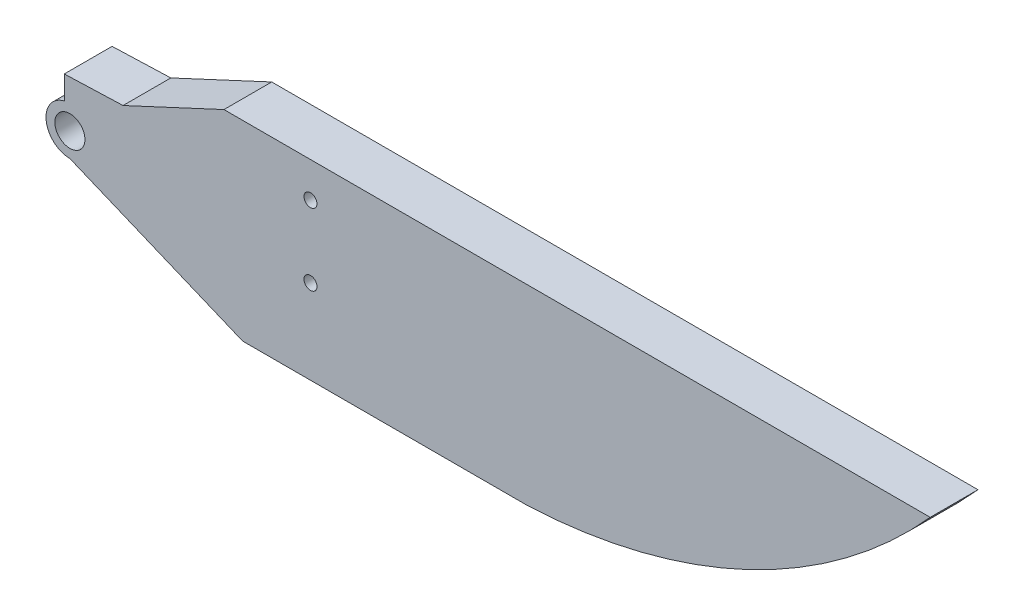
SolidWorks part; units mm, degrees
ref_plane "Front Plane" through (0, 0, 0) normal (0, 0, 1) x (1, 0, 0)
ref_plane "Top Plane" through (0, 0, 0) normal (0, 1, 0) x (1, 0, 0)
ref_plane "Right Plane" through (0, 0, 0) normal (1, 0, 0) x (0, 0, -1)
sketch "Sketch1" plane through (0, 0, 0) normal (0, 0, 1) x (1, 0, 0)
  line L1 (120.65, 25.4) -> (-120.65, 25.4)
  line L2 (120.65, 25.4) -> (120.65, -25.4)
  line L3 (120.65, -25.4) -> (-120.65, -25.4)
  line L4 (-120.65, 25.4) -> (-120.65, -25.4)
  line L5 (120.65, 25.4) -> (-120.65, -25.4) construction
  line L6 (120.65, -25.4) -> (-120.65, 25.4) construction
  point P0 (0, 0)
  dimension "D1" = 241.3
  dimension "D2" = 50.8
extrude "Boss-Extrude1" add sketch "Sketch1" along normal blind 12.7
sketch "Sketch3" plane through (0, 0, 12.7) normal (0, 0, 1) x (1, 0, 0)
  line L0 (0, 0) -> (-120.65, 0) construction
  line L1 (-120.65, 25.4) -> (-120.65, -25.4) construction
  circle A0 centre (-107.95, 0) radius 4
  dimension "D2" = 8
  dimension "D1" = 12.7
extrude "Cut-Extrude1" cut sketch "Sketch3" against normal through all
sketch "Sketch5" plane through (0, 0, 12.7) normal (0, 0, 1) x (1, 0, 0)
  line L0 (-120.65, -25.4) -> (120.65, -25.4) construction
  line L1 (-107.95, -6.35) -> (-62.0461, -25.4)
  line L2 (-107.95, 6.35) -> (-67.0151, 25.4)
  line L3 (120.65, 25.4) -> (-120.65, 25.4) construction
  line L4 (-67.0151, 25.4) -> (-120.65, 25.4)
  line L5 (-120.65, 25.4) -> (-120.65, -25.4)
  line L6 (-120.65, -25.4) -> (-62.0461, -25.4)
  line L7 (120.65, 25.4) -> (120.65, -25.4)
  line L8 (120.65, -25.4) -> (0, -25.4)
  arc A0 (0, -25.4) -> (120.65, 25.4) centre (6.9175, 126.8429) ccw
  arc A2 (-107.95, 6.35) -> (-107.95, -6.35) centre (-107.95, 0) ccw
  line M3 (-120.65, 25.4) -> (-120.65, -25.4)
  line M4 (-120.65, -25.4) -> (120.65, -25.4)
  line M5 (120.65, -25.4) -> (120.65, 25.4)
  line M6 (120.65, 25.4) -> (-120.65, 25.4)
  dimension "D1" = 152.4
  dimension "D2" = 12.7
extrude "Cut-Extrude2" cut sketch "Sketch5" against normal through all contours A2 L2 L1 M6 M3 M4 | A0 L8 M5 region at (-85.2953, -16.5913, 12.7) region at (93.5193, -10.6939, 12.7)
sketch "Sketch6" plane through (0, 0, 12.7) normal (0, 0, 1) x (1, 0, 0)
  line L0 (-107.95, 0) -> (91.396, 0) construction
  arc A0 (13.8349, -25.4) -> (120.65, 25.4) centre (6.9175, 126.8429) ccw construction
  circle A1 centre (19.05, 0) radius 3.1347
  dimension "D1" = 127
sketch "Sketch7" plane through (0, 0, 0) normal (0, 0, -1) x (-1, 0, 0)
  line L0 (44.0204, -2.9977) -> (44.0204, 16.0523) construction
  point P3 (44.0204, -2.9977)
  point P4 (44.0204, 16.0523)
  dimension "D1" = 19.05
sketch "Sketch8" plane through (0, 0, 0) normal (0, 0, -1) x (-1, 0, 0)
  point P0 (44.0204, 16.0523)
  point P3 (44.0204, -2.9977)
hole_wizard "Tap Drill for #8-32 Tap1" positions "Sketch8" profile "Sketch9" hole size "#8-32" standard "ANSI Inch" end condition through all
sketch "Sketch9" plane through (-44.0204, 16.0523, 0) normal (1, 0, 0) x (0, 1, 0)
  line L0 (0, 0) -> (0, 12.7)
  line L1 (0, 12.7) -> (1.7272, 12.7)
  line L2 (1.7272, 12.7) -> (1.7272, 0)
  line L5 (1.7272, 0) -> (0, 0)
  line L11 (0, -6.35) -> (0, 107.95) construction
  dimension "Thru Hole Dia." = 3.4544
  dimension "Thru Hole Depth" = 12.7
ref_plane "Plane1" through (-114.3, 0, 0) normal (-1, 0, 0) x (0, 0, 1)
sketch "Sketch10" plane through (-114.3, 0, 0) normal (-1, 0, 0) x (0, 0, 1)
  line L0 (0, 0) -> (12.7, 0) construction
  line L1 (12.7, -3.1347) -> (12.7, 3.1347) construction
  circle A0 centre (6.0894, 0) radius 1.905
  dimension "D1" = 3.81
extrude "Cut-Extrude3" cut sketch "Sketch10" against normal blind 5.08
sketch "Sketch11" plane through (0, 0, 12.7) normal (0, 0, 1) x (1, 0, 0)
  line L0 (-93.8249, 12.9234) -> (-109.4459, 12.9234) construction
  line L1 (-107.95, 6.35) -> (-67.0151, 25.4) construction
  line L2 (-109.4459, 12.9234) -> (-109.4459, 5.6538) construction
  line L3 (-93.8249, 12.9234) -> (-109.4459, 5.6538)
  line L4 (-93.8249, 12.9234) -> (-109.4459, 12.3779)
  line L5 (-109.4459, 12.3779) -> (-109.4459, 5.6538)
  circle A1 centre (-107.95, 0) radius 4 construction
  dimension "D1" = 15.621
  dimension "D2" = 5.6538
  dimension "D3" = 178
extrude "Boss-Extrude2" add sketch "Sketch11" against normal up to surface (12.7 mm away) up to face at (-45.7476, 16.0523, 0)
